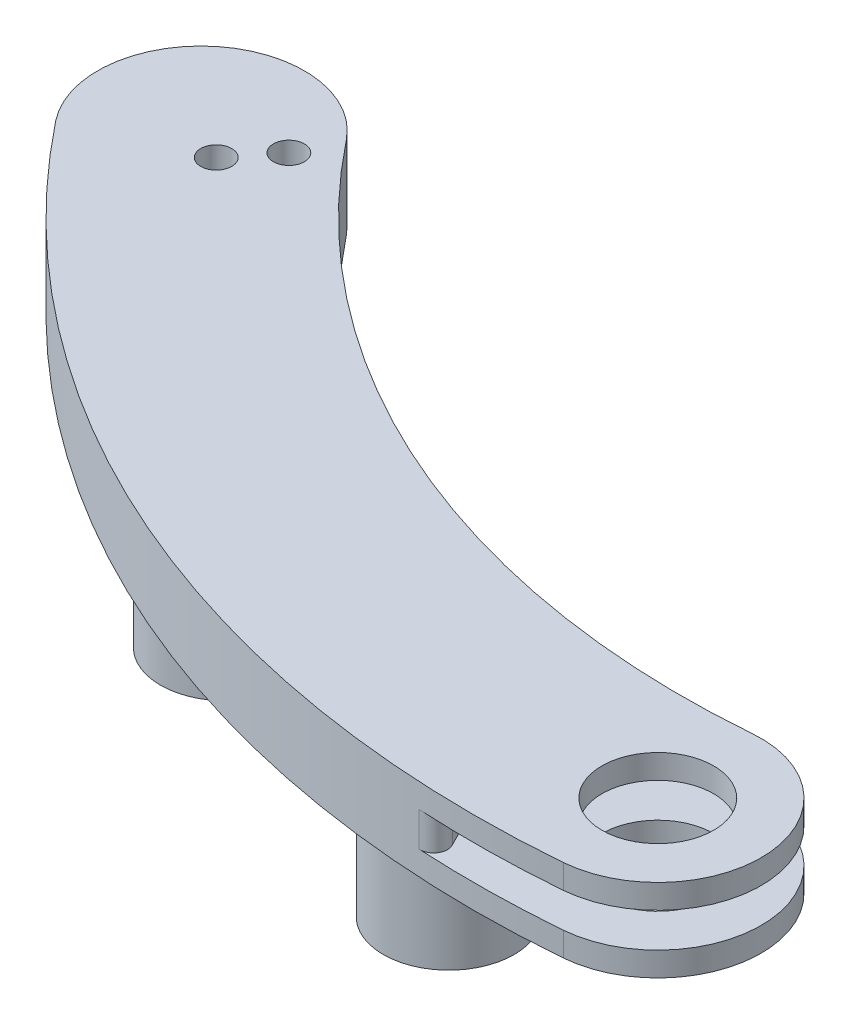
SolidWorks part; units mm, degrees
ref_plane "Front Plane" through (0, 0, 0) normal (0, 0, 1) x (1, 0, 0)
ref_plane "Top Plane" through (0, 0, 0) normal (0, 1, 0) x (1, 0, 0)
ref_plane "Right Plane" through (0, 0, 0) normal (1, 0, 0) x (0, 0, -1)
sketch "Sketch1" plane through (0, 0, 0) normal (0, 1, 0) x (1, 0, 0)
  arc A0 (0, 0) -> (-117, 50.7404) centre (-11.1561, 134.5383) cw construction
  arc A1 (-128.7604, 41.4296) -> (1.2396, -14.9487) centre (-11.1561, 134.5383) ccw
  arc A2 (-105.2396, 60.0513) -> (-1.2396, 14.9487) centre (-11.1561, 134.5383) ccw
  arc A3 (-105.2396, 60.0513) -> (-128.7604, 41.4296) centre (-117, 50.7404) ccw
  arc A4 (1.2396, -14.9487) -> (-1.2396, 14.9487) centre (0, 0) ccw
  arc A5 (-16.6792, 14.6654) -> (-15.4249, -15.401) centre (4.9458, 0.5082) ccw
  point P3 (-64.8692, 10.6839)
  dimension "D3" = 30
  dimension "D4" = 150
  dimension "D1" = 75
  dimension "D2" = 130
extrude "Boss-Extrude4" add sketch "Sketch1" along normal blind 12 contours A5 A2 A3 A1 region at (-76.6272, 0, -21.3687)
extrude "Boss-Extrude5" add sketch "Sketch1<6>" along normal blind 3.5 contours A2 A5 A1 A4 region at (-3.6374, 0, 0.1249)
sketch "Sketch1<6>" plane through (0, 0, 0) normal (0, 1, 0) x (1, 0, 0) same geometry as "Sketch1"
extrude "Boss-Extrude6" add sketch "Sketch1<8>" along normal blind 12 contours A2 A5 A1 A4 region at (-3.6374, 0, 0.1249)
sketch "Sketch1<8>" plane through (0, 0, 0) normal (0, 1, 0) x (1, 0, 0) same geometry as "Sketch1"
extrude "Cut-Extrude2" cut sketch "Sketch1<9>" along normal blind 8.5 contours A2 A5 A1 A4 region at (-3.6374, 0, 0.1249)
sketch "Sketch1<9>" plane through (0, 0, 0) normal (0, 1, 0) x (1, 0, 0) same geometry as "Sketch1"
extrude "Boss-Extrude7" add sketch "Sketch1<10>" along normal blind 3.5 contours A2 A5 A1 A4 region at (-3.6374, 0, 0.1249)
sketch "Sketch1<10>" plane through (0, 0, 0) normal (0, 1, 0) x (1, 0, 0) same geometry as "Sketch1"
sketch "Sketch2" plane through (0, 12, 0) normal (0, 1, 0) x (1, 0, 0)
  circle A0 centre (0, 0) radius 8.1
  dimension "D1" = 16.2
extrude "Cut-Extrude3" cut sketch "Sketch2" against normal blind 12
fillet "Fillet1" radius 5 1 edges at (-16.6792, 6, -14.6654)
fillet "Fillet2" radius 2 1 edges at (-15.4249, 6, 15.401)
sketch "Sketch3" plane through (0, 12, 0) normal (0, 1, 0) x (1, 0, 0)
  circle A0 centre (-107.8166, 54.3025) radius 2.25
  circle A1 centre (-112.4991, 48.4438) radius 2.25
  dimension "D1" = 4.5
  dimension "D2" = 4.5
  dimension "D3" = 7.5
  dimension "D4" = 6.3
extrude "Cut-Extrude4" cut sketch "Sketch3" against normal blind 12
sketch "Sketch4" plane through (0, 0, 0) normal (0, 1, 0) x (1, 0, 0)
  circle A0 centre (-32.2472, 1.9278) radius 8.1
  circle A1 centre (-32.2472, 1.9278) radius 9.5
  circle A2 centre (-82.2472, 19.6043) radius 8.1
  circle A3 centre (-82.2472, 19.6043) radius 9.5
  dimension "D1" = 16.2
  dimension "D2" = 19
  dimension "D3" = 50
extrude "Boss-Extrude8" add sketch "Sketch4" against normal blind 20
